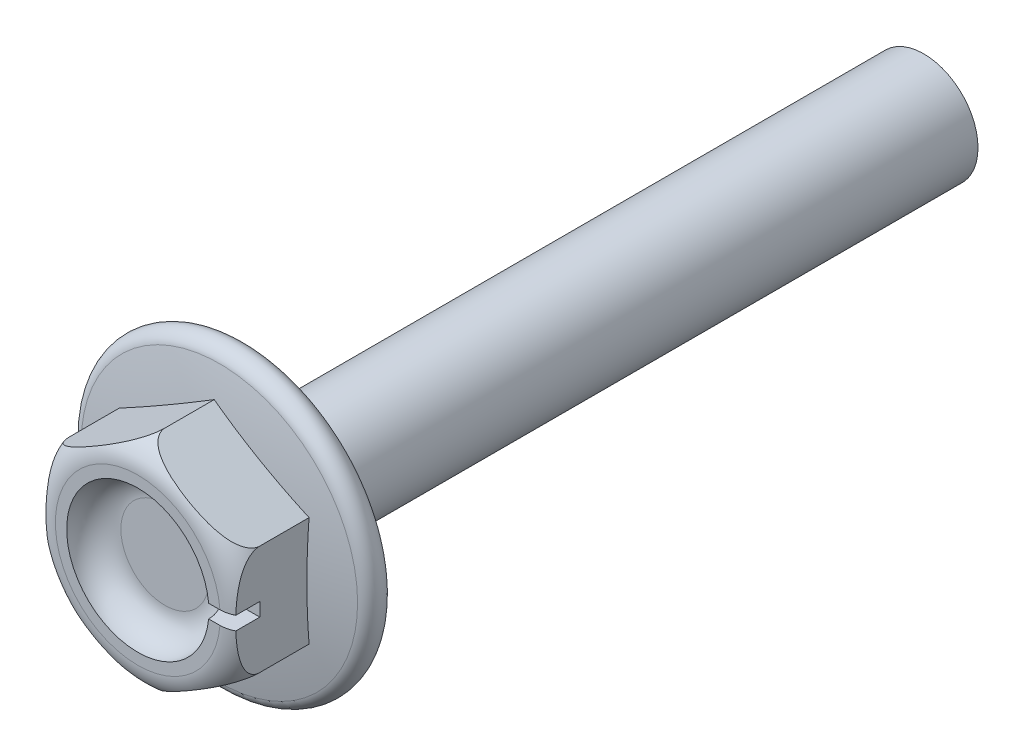
SolidWorks part; units mm, degrees
extrude "Shank" add sketch "Shank Sketch" against normal blind 25
sketch "Shank Sketch" plane through (0, 0, 0) normal (0, 0, 1) x (1, 0, 0)
  line L0 (50, 0) -> (-50, 0) construction
  line L1 (0, -50) -> (0, 50) construction
  circle A0 centre (0, 0) radius 2
  dimension "Shank diameter" = 4
extrude "Head" add sketch "Head Sketch" along normal blind 4
sketch "Head Sketch" plane through (0, 0, 0) normal (0, 0, 1) x (1, 0, 0)
  line L0 (0, 4.0415) -> (3.5, 2.0207)
  line L1 (3.5, 2.0207) -> (3.5, -2.0207)
  line L2 (3.5, -2.0207) -> (0, -4.0415)
  line L3 (0, -4.0415) -> (-3.5, -2.0207)
  line L4 (-3.5, -2.0207) -> (-3.5, 2.0207)
  line L5 (-3.5, 2.0207) -> (0, 4.0415)
  line L6 (3.5, 2.0207) -> (-3.5, -2.0207) construction
  line L7 (0, 4.0415) -> (0, -4.0415) construction
  line L8 (-3.5, 2.0207) -> (3.5, -2.0207) construction
  point P0 (0, 0)
  dimension "D1" = 60
  dimension "D2" = 60
  dimension "Width across flats" = 7
ref_plane "Plane1" through (0, 0, 0) normal (0, 0, 1) x (1, 0, 0)
ref_plane "Plane2" through (0, 0, 0) normal (0, 1, 0) x (-1, 0, 0)
ref_plane "Plane3" through (0, 0, 0) normal (1, 0, 0) x (0, 0, -1)
other "Configuration Table"
sketch "Sketch3" plane through (0, 0, 0) normal (0, 1, 0) x (-1, 0, 0)
  line L0 (0, 0) -> (0, 3) construction
  line L1 (0, -25) -> (0, 0) construction
  line L4 (-5, 0) -> (0, 0)
  line L5 (0, 0) -> (0, 1.5)
  arc A0 (0, 1.5) -> (-5.099, 0.9901) centre (0, -24.25) ccw
  arc A1 (-5, 0) -> (-5.099, 0.9901) centre (-5, 0.5) cw
  dimension "D1" = 0.5
  dimension "D2" = 10
  dimension "D3" = 1.5
revolve "Flange" add sketch "Sketch3" angle 360 about L0
sketch "Sketch5" plane through (0, 0, 0) normal (1, 0, 0) x (0, 0, -1)
  line L0 (-4, -3.0415) -> (-4, -4.0415)
  line L1 (-4, -4.0415) -> (-3, -4.0415)
  line L2 (-4, -4.0415) -> (-1.1809, -4.0415) construction
  line L3 (-4, -4.0415) -> (-4, -2.0207) construction
  line L5 (-15.0856, 0) -> (-8.1394, 0) construction
  line L6 (50, 0) -> (-50, 0) construction
  arc A0 (-4, -3.0415) -> (-3, -4.0415) centre (-3, -3.0415) ccw
  dimension "D1" = 1
revolve "Head Trim" cut sketch "Sketch5" angle 360 about L5
sketch "Sketch6" plane through (0, 0, 4) normal (0, 0, 1) x (1, 0, 0)
  circle A3 centre (0, 0) radius 2.625
  dimension "D1" = 5.25
extrude "Head Cut" cut sketch "Sketch6" against normal blind 1
fillet "Fillet1" radius 1 1 edges at (2.625, 0, 3)
sketch "Sketch7" plane through (0.7418, 1.4072, 4) normal (0, 0, 1) x (1, 0, 0)
  line L0 (-0.7418, -1.4072) -> (2.7582, -1.4072) construction
  line L2 (-0.7418, -1.1572) -> (-0.7418, -1.6572)
  line L3 (-0.7418, -1.6572) -> (2.7582, -1.6572)
  line L5 (-0.7418, -1.1572) -> (2.7582, -1.1572)
  line L6 (2.7582, -1.6572) -> (2.7582, -1.1572)
  line L8 (2.7582, -3.4279) -> (2.7582, 0.6135) construction
  circle A1 centre (-0.7418, -1.4072) radius 1.625 construction
  dimension "D1" = 0.5
extrude "Cut-Extrude1" cut sketch "Sketch7" against normal blind 1
equation "\"D1@Sketch6\" = \"Width across flats@Head Sketch\"*3/4"
